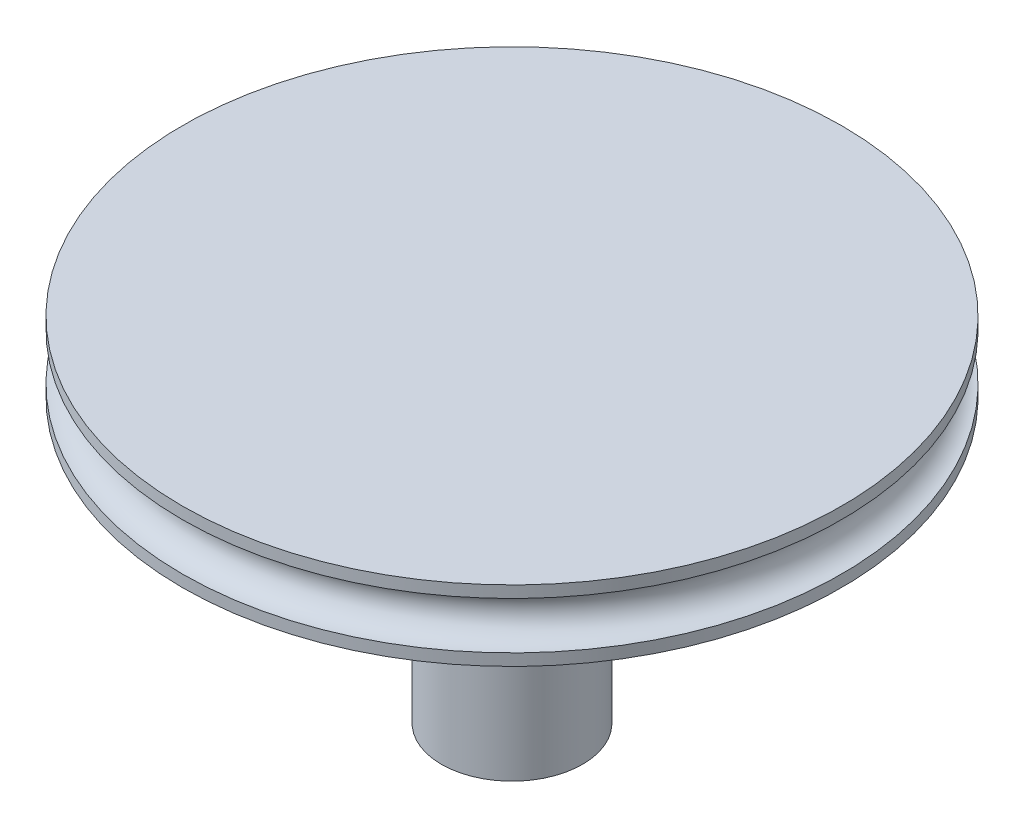
SolidWorks part; units mm, degrees
ref_plane "Front Plane" through (0, 0, 0) normal (0, 0, 1) x (1, 0, 0)
ref_plane "Top Plane" through (0, 0, 0) normal (0, 1, 0) x (1, 0, 0)
ref_plane "Right Plane" through (0, 0, 0) normal (1, 0, 0) x (0, 0, -1)
ref_axis "Axis1" through (0, 3.6, 0) along (0, -1, 0)
sketch "Sketch1" plane through (0, 0, 0) normal (0, 0, 1) x (1, 0, 0)
  line L0 (3, 0) -> (14, 0)
  line L1 (14, 3) -> (14, 2.5)
  line L2 (14, 3) -> (0, 3)
  line L3 (0, 3) -> (0, -12)
  line L4 (0, -12) -> (3, -12)
  line L5 (3, -12) -> (3, 0)
  line L6 (14, 0) -> (14, 0.5)
  arc A0 (14, 2.5) -> (14, 0.5) centre (14, 1.5) ccw
  point P10 (16.2215, 1)
  point P11 (0, 0)
  point P12 (16.5989, 2.3694)
  point P13 (14, 0.5)
  point P14 (14, 0)
  point P15 (14, 1.5)
  point P16 (14, 2.5)
  point P17 (14, 0)
  point P18 (14, 0)
  point P19 (14, 0.5)
  dimension "D2" = 1
  dimension "D1" = 0.5
  dimension "D3" = 3
  dimension "D4" = 14
  dimension "D5" = 3
  dimension "D6" = 15
revolve "Revolve1" add sketch "Sketch1" angle 360 about axis through (0, 3.6, 0) along (0, -1, 0)
